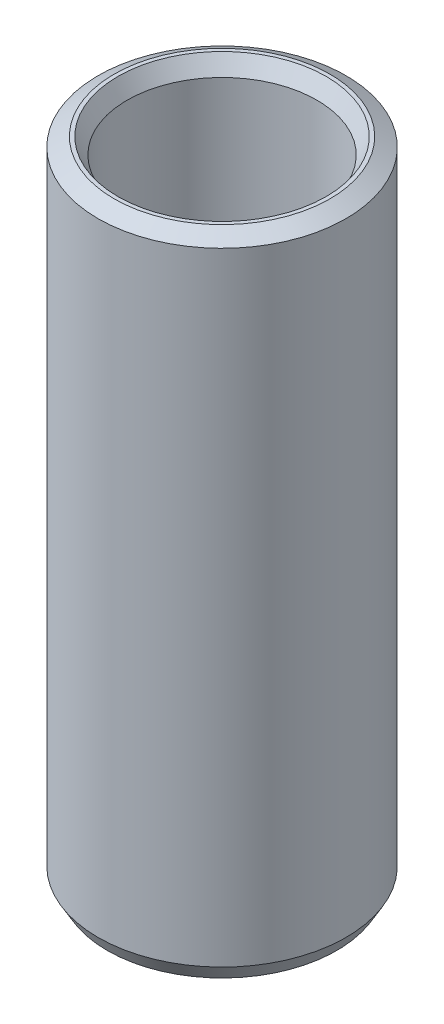
SolidWorks part; units mm, degrees
ref_plane "Front Plane" through (0, 0, 0) normal (0, 0, 1) x (1, 0, 0)
ref_plane "Top Plane" through (0, 0, 0) normal (0, 1, 0) x (1, 0, 0)
ref_plane "Right Plane" through (0, 0, 0) normal (1, 0, 0) x (0, 0, -1)
sketch "Sketch1" plane through (0, 0, 0) normal (0, 1, 0) x (1, 0, 0)
  circle A0 centre (0, 0) radius 17.5
  dimension "SLEEVE_OD" = 35
extrude "Boss-Extrude1" add sketch "Sketch1" along normal blind 91.4531
sketch "Sketch2" plane through (0, 0, 0) normal (0, 1, 0) x (1, 0, 0)
  circle A0 centre (0, 0) radius 13.4012
  dimension "BORE_D" = 26.8025
extrude "Cut-Extrude1" cut sketch "Sketch2" along normal through all
chamfer "Chamfer1" distance 1.3014 angle 60 4 edges at (0, 91.4531, 13.4012) (0, 0, 13.4012) (0, 0, 17.5) (0, 91.4531, 17.5) first distance on face at (0, 91.4531, 13.4012) first distance on face at (0, 0, 13.4012) first distance on face at (0, 91.4531, 17.5)
